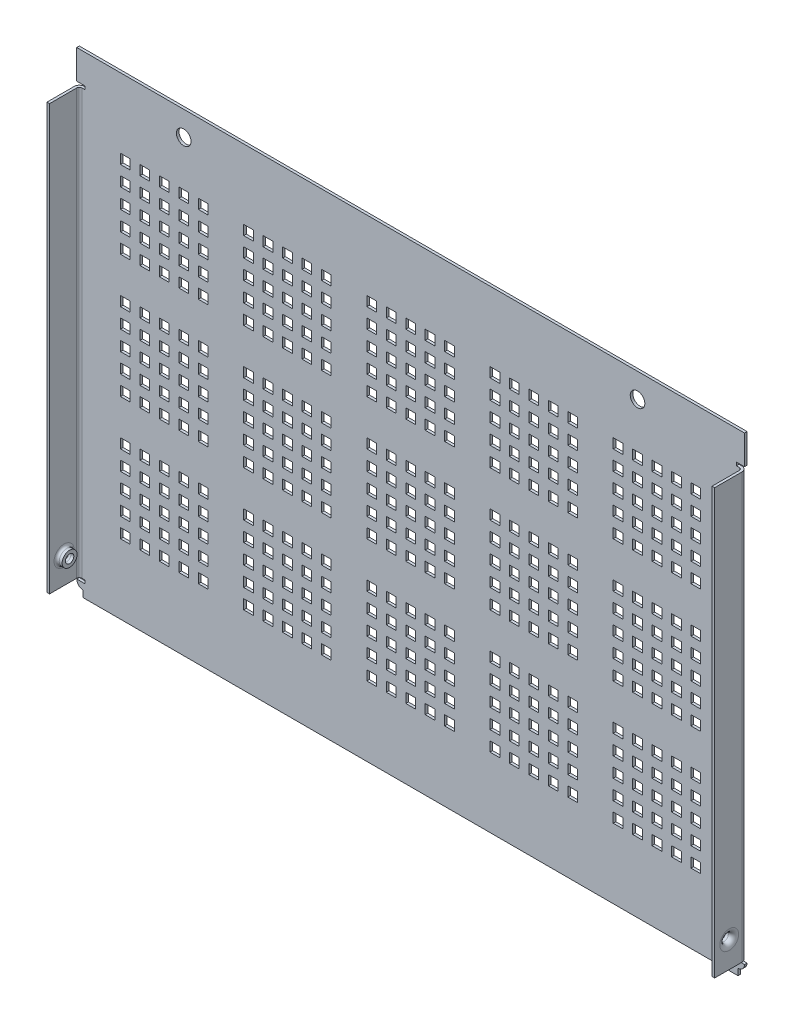
SolidWorks part; units mm, degrees
ref_plane "Спереди" through (0, 0, 0) normal (0, 0, 1) x (1, 0, 0)
ref_plane "Сверху" through (0, 0, 0) normal (0, 1, 0) x (1, 0, 0)
ref_plane "Справа" through (0, 0, 0) normal (1, 0, 0) x (0, 0, -1)
sketch "Эскиз1" plane through (0, 0, 0) normal (0, 0, 1) x (1, 0, 0)
  line L0 (0, 0) -> (62.4314, 0) construction
  line L1 (0, 0) -> (0, 65.1311) construction
  line L2 (-85.9833, 65.5) -> (87.5627, 65.5) construction
  line L3 (-101, -73) -> (101, -73)
  line L4 (-103, -69) -> (-103, 73)
  line L5 (-103, 73) -> (103, 73)
  line L6 (103, -69) -> (103, 73)
  line L7 (101, -71) -> (101, -73)
  line L9 (-101, -71) -> (-101, -73)
  circle A0 centre (-70, 65.5) radius 2.25
  circle A1 centre (70, 65.5) radius 2.25
  arc A2 (-103, -69) -> (-101, -71) centre (-101, -69) ccw
  arc A3 (103, -69) -> (101, -71) centre (101, -69) cw
  point P16 (-103, -73)
  dimension "D4" = 140
  dimension "D5" = 4.5
  dimension "D6" = 2
  dimension "D8" = 2
  dimension "D7" = 4
  dimension "D1" = 206
  dimension "D2" = 146
  dimension "D3" = 7.5
extrude "Вытянуть1" add sketch "Эскиз1" along normal blind 0.8
sketch "Эскиз2" plane through (0, 0, 0.8) normal (0, 0, 1) x (1, 0, 0)
  line L0 (-103, 73) -> (-103, -69) construction
  line L1 (-103, -68) -> (-102.2, -68)
  line L2 (-103, -68) -> (-103, 63)
  line L3 (-103, 63) -> (-102.2, 63)
  line L4 (-102.2, -68) -> (-102.2, 63)
  line L5 (103, 73) -> (-103, 73) construction
  line L6 (-101, -73) -> (101, -73) construction
  line L7 (0, -78.3079) -> (0, 89.5433) construction
  line L8 (102.2, -68) -> (102.2, 63)
  line L9 (103, 63) -> (102.2, 63)
  line L10 (103, -68) -> (103, 63)
  line L11 (103, -68) -> (102.2, -68)
  dimension "D1" = 0.8
  dimension "D2" = 10
  dimension "D3" = 5
extrude "Вытянуть2" add sketch "Эскиз2" along normal blind 9.2
sketch "Эскиз3" plane through (0, 0, 0.8) normal (0, 0, 1) x (1, 0, 0)
  line L0 (-102.2, 63) -> (-103, 63) construction
  line L1 (-104.5884, 63) -> (-100.5, 63)
  line L2 (-104.5884, 63) -> (-104.5884, 64)
  line L3 (-104.5884, 64) -> (-100.5, 64)
  line L4 (-100.5, 63) -> (-100.5, 64)
  line L5 (-103, 73) -> (-103, 63) construction
  line L6 (-137.1911, -2.5) -> (-34.5187, -2.5) construction
  line L7 (0, 0) -> (0, 51.2111) construction
  line L8 (-103, -68) -> (-102.2, -68) construction
  line L9 (-100.5, -68) -> (-100.5, -69)
  line L10 (-104.5884, -69) -> (-100.5, -69)
  line L11 (-104.5884, -68) -> (-104.5884, -69)
  line L12 (-104.5884, -68) -> (-100.5, -68)
  line L13 (104.5884, -68) -> (100.5, -68)
  line L14 (104.5884, -68) -> (104.5884, -69)
  line L15 (104.5884, -69) -> (100.5, -69)
  line L16 (100.5, -68) -> (100.5, -69)
  line L17 (100.5, 63) -> (100.5, 64)
  line L18 (104.5884, 64) -> (100.5, 64)
  line L19 (104.5884, 63) -> (104.5884, 64)
  line L20 (104.5884, 63) -> (100.5, 63)
  dimension "D1" = 1
  dimension "D2" = 2.5
extrude "Вырез-Вытянуть1" cut sketch "Эскиз3" against normal blind 5
fillet "Скругление1" radius 0.8 2 edges at (102.2, -2.5, 0.8) (-102.2, -2.5, 0.8)
fillet "Скругление2" radius 1.6 2 edges at (-103, -2.5, 0) (103, -2.5, 0)
sketch "Эскиз4" plane through (-103, 0, 0) normal (-1, 0, 0) x (0, 0, 1)
  line L0 (5.5, -64.195) -> (5.5, -40.2952) construction
  line L1 (10, 63) -> (10, -68) construction
  line L2 (10, -68) -> (1.6, -68) construction
  circle A0 centre (5.5, -60) radius 2.3
  dimension "D3" = 4.6
  dimension "D1" = 4.5
  dimension "D2" = 8
extrude "Вытянуть3" add sketch "Эскиз4" against normal blind 2.5
sketch "Эскиз5" plane through (-103, 0, 0) normal (-1, 0, 0) x (0, 0, 1)
  circle A0 centre (5.5, -60) radius 1.3
  circle A1 centre (5.5, -60) radius 2.3 construction
  dimension "D1" = 2.6
extrude "Вырез-Вытянуть2" cut sketch "Эскиз5" against normal blind 300
cosmetic thread "Условное изображение резьбы1" parameters "D1"=3, "D2"=3
cosmetic thread "Условное изображение резьбы2" parameters "D1"=3, "D2"=3
fillet "Скругление3" radius 1.6 1 edges at (-103, -61.3, 5.5)
fillet "Скругление4" radius 0.8 1 edges at (-102.2, -60, 7.8)
sketch "Эскиз6" plane through (103, 0, 0) normal (1, 0, 0) x (0, 0, -1)
  circle A0 centre (-5.5, -60) radius 2.3
  circle A1 centre (-5.5, -60) radius 1.3 construction
  circle A2 centre (-5.5, -60) radius 1.3
  dimension "D1" = 4.6
extrude "Вытянуть4" add sketch "Эскиз6" against normal blind 2.5
fillet "Скругление5" radius 0.8 1 edges at (102.2, -60, 3.2)
fillet "Скругление6" radius 1.6 1 edges at (103, -61.3, 5.5)
sketch "Эскиз7" plane through (0, 0, 0) normal (0, 0, -1) x (-1, 0, 0)
  line L0 (0, 14.789) -> (0, -13.7982) construction
  line L1 (-16.1559, 0) -> (12.1335, 0) construction
  line L2 (4.5, -1.5) -> (7.5, -1.5)
  line L3 (-1.5, -1.5) -> (1.5, -1.5)
  line L4 (-1.5, -1.5) -> (-1.5, 1.5)
  line L5 (-1.5, 1.5) -> (1.5, 1.5)
  line L6 (1.5, -1.5) -> (1.5, 1.5)
  line L7 (4.5, -1.5) -> (4.5, 1.5)
  line L8 (4.5, 1.5) -> (7.5, 1.5)
  line L9 (7.5, -1.5) -> (7.5, 1.5)
  line L10 (10.5, -1.5) -> (13.5, -1.5)
  line L11 (10.5, -1.5) -> (10.5, 1.5)
  line L12 (10.5, 1.5) -> (13.5, 1.5)
  line L13 (13.5, -1.5) -> (13.5, 1.5)
  line L14 (-7.5, -1.5) -> (-4.5, -1.5)
  line L15 (-7.5, -1.5) -> (-7.5, 1.5)
  line L16 (-7.5, 1.5) -> (-4.5, 1.5)
  line L17 (-4.5, -1.5) -> (-4.5, 1.5)
  line L18 (-13.5, -1.5) -> (-10.5, -1.5)
  line L19 (-13.5, -1.5) -> (-13.5, 1.5)
  line L20 (-13.5, 1.5) -> (-10.5, 1.5)
  line L21 (-10.5, -1.5) -> (-10.5, 1.5)
  line L22 (4.5, 4.5) -> (7.5, 4.5)
  line L23 (-1.5, 4.5) -> (1.5, 4.5)
  line L24 (-1.5, 4.5) -> (-1.5, 7.5)
  line L25 (-1.5, 7.5) -> (1.5, 7.5)
  line L26 (1.5, 4.5) -> (1.5, 7.5)
  line L27 (4.5, 4.5) -> (4.5, 7.5)
  line L28 (4.5, 7.5) -> (7.5, 7.5)
  line L29 (7.5, 4.5) -> (7.5, 7.5)
  line L30 (10.5, 4.5) -> (13.5, 4.5)
  line L31 (10.5, 4.5) -> (10.5, 7.5)
  line L32 (10.5, 7.5) -> (13.5, 7.5)
  line L33 (13.5, 4.5) -> (13.5, 7.5)
  line L34 (-7.5, 4.5) -> (-4.5, 4.5)
  line L35 (-7.5, 4.5) -> (-7.5, 7.5)
  line L36 (-7.5, 7.5) -> (-4.5, 7.5)
  line L37 (-4.5, 4.5) -> (-4.5, 7.5)
  line L38 (-13.5, 4.5) -> (-10.5, 4.5)
  line L39 (-13.5, 4.5) -> (-13.5, 7.5)
  line L40 (-13.5, 7.5) -> (-10.5, 7.5)
  line L41 (-10.5, 4.5) -> (-10.5, 7.5)
  line L42 (-16.1559, 6) -> (12.1335, 6) construction
  line L43 (4.5, 10.5) -> (7.5, 10.5)
  line L44 (-1.5, 10.5) -> (1.5, 10.5)
  line L45 (-1.5, 10.5) -> (-1.5, 13.5)
  line L46 (-1.5, 13.5) -> (1.5, 13.5)
  line L47 (1.5, 10.5) -> (1.5, 13.5)
  line L48 (4.5, 10.5) -> (4.5, 13.5)
  line L49 (4.5, 13.5) -> (7.5, 13.5)
  line L50 (7.5, 10.5) -> (7.5, 13.5)
  line L51 (10.5, 10.5) -> (13.5, 10.5)
  line L52 (10.5, 10.5) -> (10.5, 13.5)
  line L53 (10.5, 13.5) -> (13.5, 13.5)
  line L54 (13.5, 10.5) -> (13.5, 13.5)
  line L55 (-7.5, 10.5) -> (-4.5, 10.5)
  line L56 (-7.5, 10.5) -> (-7.5, 13.5)
  line L57 (-7.5, 13.5) -> (-4.5, 13.5)
  line L58 (-4.5, 10.5) -> (-4.5, 13.5)
  line L59 (-13.5, 10.5) -> (-10.5, 10.5)
  line L60 (-13.5, 10.5) -> (-13.5, 13.5)
  line L61 (-13.5, 13.5) -> (-10.5, 13.5)
  line L62 (-10.5, 10.5) -> (-10.5, 13.5)
  line L63 (-16.1559, 12) -> (12.1335, 12) construction
  line L64 (4.5, -7.5) -> (7.5, -7.5)
  line L65 (-1.5, -7.5) -> (1.5, -7.5)
  line L66 (-1.5, -7.5) -> (-1.5, -4.5)
  line L67 (-1.5, -4.5) -> (1.5, -4.5)
  line L68 (1.5, -7.5) -> (1.5, -4.5)
  line L69 (4.5, -7.5) -> (4.5, -4.5)
  line L70 (4.5, -4.5) -> (7.5, -4.5)
  line L71 (7.5, -7.5) -> (7.5, -4.5)
  line L72 (10.5, -7.5) -> (13.5, -7.5)
  line L73 (10.5, -7.5) -> (10.5, -4.5)
  line L74 (10.5, -4.5) -> (13.5, -4.5)
  line L75 (13.5, -7.5) -> (13.5, -4.5)
  line L76 (-7.5, -7.5) -> (-4.5, -7.5)
  line L77 (-7.5, -7.5) -> (-7.5, -4.5)
  line L78 (-7.5, -4.5) -> (-4.5, -4.5)
  line L79 (-4.5, -7.5) -> (-4.5, -4.5)
  line L80 (-13.5, -7.5) -> (-10.5, -7.5)
  line L81 (-13.5, -7.5) -> (-13.5, -4.5)
  line L82 (-13.5, -4.5) -> (-10.5, -4.5)
  line L83 (-10.5, -7.5) -> (-10.5, -4.5)
  line L84 (4.5, -13.5) -> (7.5, -13.5)
  line L85 (-1.5, -13.5) -> (1.5, -13.5)
  line L86 (-1.5, -13.5) -> (-1.5, -10.5)
  line L87 (-1.5, -10.5) -> (1.5, -10.5)
  line L88 (1.5, -13.5) -> (1.5, -10.5)
  line L89 (4.5, -13.5) -> (4.5, -10.5)
  line L90 (4.5, -10.5) -> (7.5, -10.5)
  line L91 (7.5, -13.5) -> (7.5, -10.5)
  line L92 (10.5, -13.5) -> (13.5, -13.5)
  line L93 (10.5, -13.5) -> (10.5, -10.5)
  line L94 (10.5, -10.5) -> (13.5, -10.5)
  line L95 (13.5, -13.5) -> (13.5, -10.5)
  line L96 (-7.5, -13.5) -> (-4.5, -13.5)
  line L97 (-7.5, -13.5) -> (-7.5, -10.5)
  line L98 (-7.5, -10.5) -> (-4.5, -10.5)
  line L99 (-4.5, -13.5) -> (-4.5, -10.5)
  line L100 (-13.5, -13.5) -> (-10.5, -13.5)
  line L101 (-13.5, -13.5) -> (-13.5, -10.5)
  line L102 (-13.5, -10.5) -> (-10.5, -10.5)
  line L103 (-10.5, -13.5) -> (-10.5, -10.5)
  dimension "D1" = 3
  dimension "D2" = 3
extrude "Вырез-Вытянуть3" cut sketch "Эскиз7" against normal blind 10
pattern_linear "Линейный массив1" count 3 spacing 38 along (-1, 0, 0) of "Вырез-Вытянуть3"
pattern_linear "Линейный массив3" count 3 spacing 38 along (1, 0, 0) of "Вырез-Вытянуть3"
pattern_linear "Линейный массив4" count 2 spacing 38 along (0, 1, 0) of "Вырез-Вытянуть3", "Линейный массив1", "Линейный массив3"
pattern_linear "Линейный массив5" count 2 spacing 38 along (0, -1, 0) of "Вырез-Вытянуть3", "Линейный массив1", "Линейный массив3"
